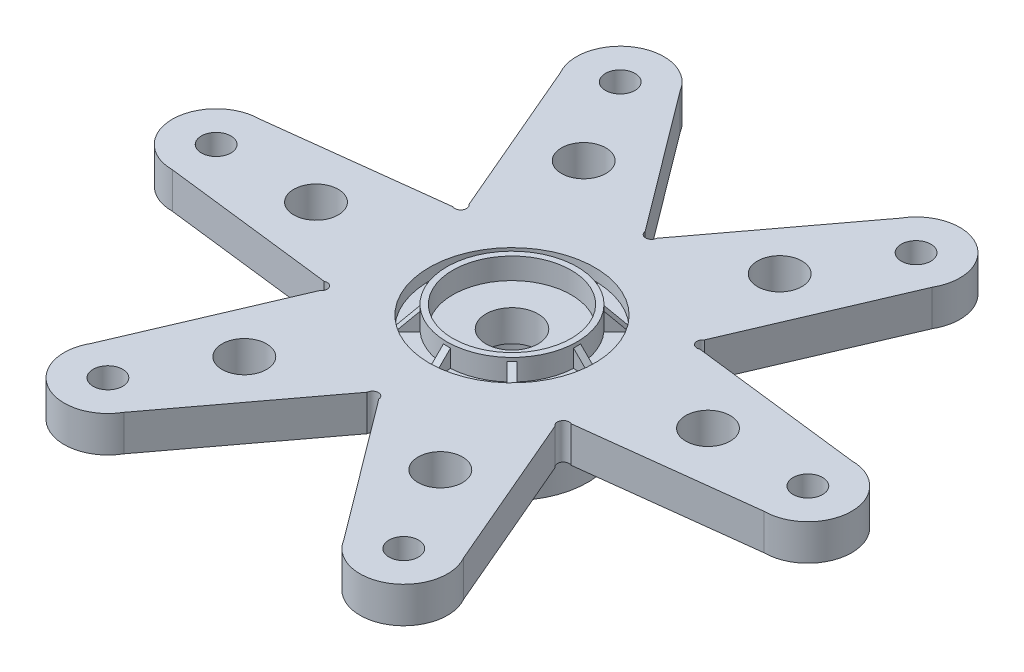
SolidWorks part; units mm, degrees
material "Delrin 2700 NC010, Low Viscosity Acetal Copolymer (SS)"
ref_plane "Front Plane" through (0, 0, 0) normal (0, 0, 1) x (1, 0, 0)
ref_plane "Top Plane" through (0, 0, 0) normal (0, 1, 0) x (1, 0, 0)
ref_plane "Right Plane" through (0, 0, 0) normal (1, 0, 0) x (0, 0, -1)
sketch "Sketch1" plane through (0, 0, 0) normal (0, 1, 0) x (1, 0, 0)
  line L0 (5.7752, -3.8298) -> (0, 0)
  line L1 (6.3503, 3.495) -> (6.3503, 3.8298)
  line L2 (6.3497, -3.4899) -> (15.8747, -2.3469)
  line L3 (6.3503, 3.495) -> (15.8747, 2.3521)
  line L4 (5.7752, 3.8298) -> (0, 0)
  line L5 (6.3503, 3.8298) -> (5.7752, 3.8298)
  line L6 (6.3497, -3.4899) -> (6.3497, -3.8298)
  line L7 (6.3497, -3.8298) -> (5.7752, -3.8298)
  arc A0 (15.8747, -2.3469) -> (15.8747, 2.3521) centre (15.8747, 0.0026) ccw
  dimension "D2" = 4.699
extrude "Extrude4" add sketch "Sketch1" along normal blind 1.9304
sketch "Sketch2" plane through (0, 1.9304, 0) normal (0, 1, 0) x (-1, 0, 0)
  circle A0 centre (-6.3426, -4.1499) radius 0.6604
  circle A1 centre (-6.3426, 4.1499) radius 0.6604
  dimension "D1" = 1.3208
extrude "Cut-Extrude1" cut sketch "Sketch2" against normal through all contours A1 | A0
ref_axis "Axis1" through (0, 0, 0) along (0, 1, 0)
pattern_circular "CirPattern4" count 6 over 360 about axis through (0, 0, 0) along (0, 1, 0) of "Extrude4"
sketch "Sketch3" plane through (0, 1.9304, 0) normal (0, 1, 0) x (-1, 0, 0)
  circle A0 centre (0, 0) radius 1.397
  dimension "D1" = 2.794
extrude "Cut-Extrude2" cut sketch "Sketch3" against normal blind 12.7 and the other way blind 12.7
sketch "Sketch4" plane through (0, 1.9304, 0) normal (0, 1, 0) x (-1, 0, 0)
  circle A0 centre (0, 0) radius 4.445
  dimension "D1" = 8.89
extrude "Cut-Extrude3" cut sketch "Sketch4" against normal blind 0.635
sketch "Sketch5" plane through (0, 1.2954, 0) normal (0, 1, 0) x (-1, 0, 0)
  circle A0 centre (0, 0) radius 3.4925
  circle A1 centre (0, 0) radius 3.175
  dimension "D1" = 6.985
  dimension "D2" = 6.35
extrude "Extrude5" add sketch "Sketch5" along normal blind 1.143 contours A1 | A0
sketch "Sketch8" plane through (0, 0, 0) normal (0, 0, 1) x (1, 0, 0)
  line L1 (4.445, 1.2954) -> (-4.445, 1.2954) construction
  line L4 (-3.4925, 2.2448) -> (-4.443, 1.2954)
rib "Rib10" sketch "Sketch8" sketch "Sketch8" thickness 0.381 extrusion direction parallel to sketch draft on no parameters "D1"=0.381
pattern_circular "CirPattern5" count 8 over 360 about axis through (0, 0, 0) along (0, 1, 0) of "Rib10"
sketch "Sketch9" plane through (0, 1.9304, 0) normal (0, 1, 0) x (-1, 0, 0)
  line L0 (0, 0) -> (7.9351, 13.7492) construction
  circle A0 centre (7.9351, 13.7492) radius 0.7937
  circle A1 centre (5.2563, 9.1076) radius 1.1938
  dimension "D1" = 1.5875
  dimension "D3" = 2.3876
  dimension "D2" = 10.5156
extrude "Cut-Extrude4" cut sketch "Sketch9" against normal through all
pattern_circular "CirPattern6" count 6 over 360 about axis through (0, 0, 0) along (0, 1, 0) of "Cut-Extrude4"
sketch "Sketch10" plane through (0, 0, 0) normal (0, -1, 0) x (1, 0, 0)
  circle A0 centre (0, 0) radius 5.08
  dimension "D1" = 10.16
extrude "Extrude6" add sketch "Sketch10" along normal blind 0.762
fillet "Fillet2" radius 0.508 1 edges at (0, 0, 5.08)
sketch "Sketch11" plane through (0, -0.762, 0) normal (0, -1, 0) x (1, 0, 0)
  circle A0 centre (0, 0) radius 4.064
  dimension "D1" = 8.128
extrude "Extrude7" add sketch "Sketch11" along normal blind 3.048
fillet "Fillet3" radius 0.889 1 edges at (0, -0.762, -4.064)
sketch "Sketch12" plane through (0, -3.81, 0) normal (0, -1, 0) x (1, 0, 0)
  circle A0 centre (0, 0) radius 2.8575
  dimension "D1" = 5.715
extrude "Cut-Extrude5" cut sketch "Sketch12" against normal blind 3.429
sketch "Sketch14" plane through (0, -0.381, 0) normal (0, -1, 0) x (1, 0, 0)
  circle A0 centre (0, 0) radius 1.397
  dimension "D1" = 2.794
extrude "Cut-Extrude6" cut sketch "Sketch14" against normal through all
sketch "Sketch15" plane through (0, 1.9304, 0) normal (0, 1, 0) x (-1, 0, 0)
  circle A0 centre (-6.4872, -3.7519) radius 0.3175
  dimension "D1" = 0.635
extrude "Cut-Extrude7" cut sketch "Sketch15" against normal through all and the other way through all
pattern_circular "CirPattern7" count 6 over 360 about axis through (0, 0, 0) along (0, 1, 0) of "Cut-Extrude7"
